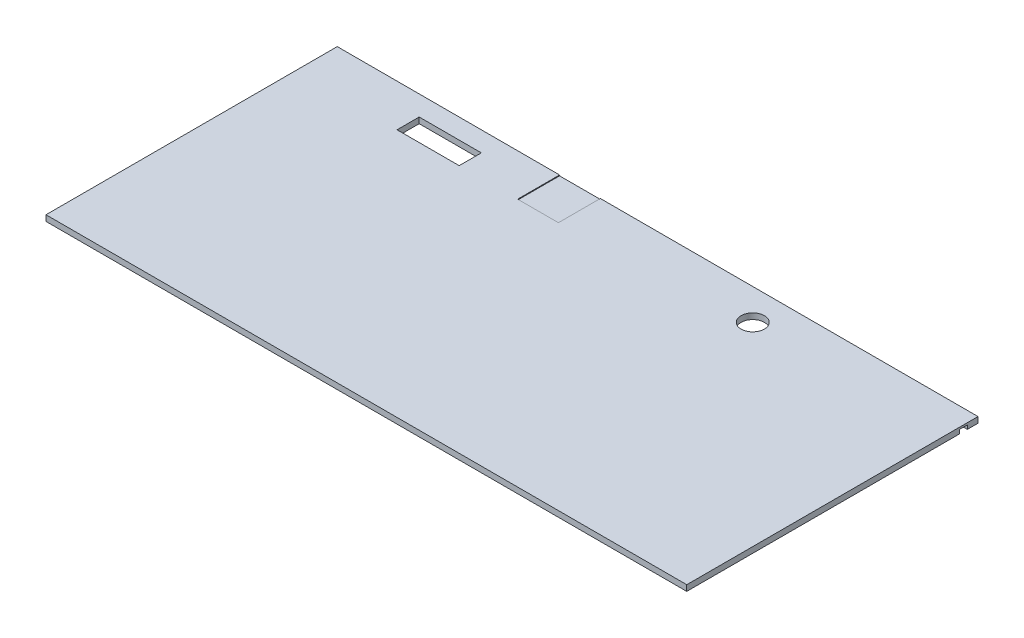
SolidWorks part; units mm, degrees
material "Oak"
ref_plane "Front Plane" through (0, 0, 0) normal (0, 0, 1) x (1, 0, 0)
ref_plane "Top Plane" through (0, 0, 0) normal (0, 1, 0) x (1, 0, 0)
ref_plane "Right Plane" through (0, 0, 0) normal (1, 0, 0) x (0, 0, -1)
sketch "Sketch1" plane through (0, 0, 0) normal (0, 1, 0) x (1, 0, 0)
  line L0 (425, 375) -> (425, -375) construction
  line L1 (-825, -375) -> (825, -375)
  line L2 (-825, -375) -> (-825, 375)
  line L3 (-825, 375) -> (825, 375)
  line L4 (825, -375) -> (825, 375)
  line L5 (-825, -375) -> (825, 375) construction
  line L6 (-825, 375) -> (825, -375) construction
  line L7 (425, 375) -> (-825, 375) construction
  line L8 (-200, 375) -> (-200, -375) construction
  line L9 (-252.5, 375) -> (-252.5, 267)
  line L10 (-252.5, 267) -> (-147.5, 267)
  line L11 (-147.5, 267) -> (-147.5, 375)
  line L12 (-482.5, 323.5) -> (-482.5, 266.5) construction
  line L13 (-562.5, 266.5) -> (-402.5, 266.5)
  line L14 (-562.5, 266.5) -> (-562.5, 323.5)
  line L15 (-562.5, 323.5) -> (-402.5, 323.5)
  line L16 (-402.5, 266.5) -> (-402.5, 323.5)
  circle A0 centre (325, 295) radius 30
  point P0 (0, 0)
  point P22 (-482.5, 295)
  dimension "D6" = 60
  dimension "D1" = 1650
  dimension "D2" = 750
  dimension "D3" = 400
  dimension "D4" = 105
  dimension "D5" = 108
  dimension "D7" = 80
  dimension "D8" = 100
  dimension "D9" = 160
  dimension "D10" = 57
  dimension "D11" = 80
  dimension "D12" = 150
extrude "Boss-Extrude1" add sketch "Sketch1" along normal blind 15 contours L11 L10 L9 L3 L2 L1 L4 A0 L16 L13 L14 L15 | L10 L11 L3 L9 region at (4.7352, 0, 5.9006) region at (-200, 0, -321)
sketch "Sketch3" plane through (0, 0, 0) normal (0, -1, 0) x (1, 0, 0)
  line L0 (-787.5, 300) -> (-787.5, -300) construction
  line L1 (-825, -375) -> (-750, -375) construction
  line L2 (-825, -375) -> (-825, -300) construction
  line L3 (-825, -300) -> (-750, -300) construction
  line L4 (-750, -375) -> (-750, -300) construction
  line L9 (7.7, 0) -> (-7.7, 0) construction
  line L10 (-825, 375) -> (-825, 300) construction
  line L11 (-825, 375) -> (-750, 375) construction
  line L12 (-750, 375) -> (-750, 300) construction
  line L13 (-825, 300) -> (-750, 300) construction
  line L14 (-777.5, 300) -> (-777.5, -300)
  line L15 (-797.5, -300) -> (-797.5, 300)
  line L16 (-797.5, 300) -> (-777.5, 300)
  line L17 (-777.5, -300) -> (-797.5, -300)
  dimension "D1" = 75
  dimension "D2" = 20
sketch "Sketch2" plane through (-825, 0, 0) normal (-1, 0, 0) x (0, 0, 1)
  line L0 (-300, 0) -> (-300, 15) construction
  line L1 (375, 0) -> (-375, 0) construction
  line L2 (375, 15) -> (-375, 15) construction
  line L3 (-375, 15) -> (-375, 0) construction
  line L4 (-300, 15) -> (-375, 15) construction
  line L5 (-337.5, 15) -> (-337.5, 0) construction
  line L6 (375, 0) -> (-375, 0) construction
  line L7 (-347.5, 0) -> (-347.5, 10)
  line L8 (-347.5, 10) -> (-327.5, 10)
  line L9 (-327.5, 10) -> (-327.5, 0)
  line L10 (-327.5, 0) -> (-347.5, 0)
  line L11 (0, -7.7) -> (0, 7.7) construction
  line L12 (347.5, 10) -> (327.5, 10)
  line L13 (347.5, 0) -> (347.5, 10)
  line L14 (327.5, 0) -> (347.5, 0)
  line L15 (327.5, 10) -> (327.5, 0)
  line M7 (-375, 0) -> (375, 0)
  dimension "D1" = 75
  dimension "D2" = 20
  dimension "D3" = 10
extrude "Cut-Extrude1" cut sketch "Sketch2" along normal up to vertex (-75 mm away) from vertex contours L9 L8 L7 M7 region at (-825, 5, -337.5) up to point (-750, 0, -300) starting at point (-252.5, 0, -375)
extrude "Cut-Extrude2" cut sketch "Sketch2<3>" against normal through all from vertex contours L9 L8 L7 M7 region at (-825, 5, -337.5) starting at point (-147.5, 0, -375)
sketch "Sketch2<3>" plane through (-825, 0, 0) normal (-1, 0, 0) x (0, 0, 1) same geometry as "Sketch2"
extrude "Cut-Extrude3" cut sketch "Sketch1<3>" along normal through all from offset 13 contours L10 L11 L3 L9 region at (-200, 0, -321)
sketch "Sketch1<3>" plane through (0, 0, 0) normal (0, 1, 0) x (1, 0, 0) same geometry as "Sketch1"
extrude "Cut-Extrude4" cut sketch "Sketch2<4>" against normal up to vertex (572.5 mm away) from vertex contours L12 L15 L13 M7 region at (-825, 5, 337.5) up to point (-252.5, 0, -267) starting at point (-750, 0, 375)
sketch "Sketch2<4>" plane through (-825, 0, 0) normal (-1, 0, 0) x (0, 0, 1) same geometry as "Sketch2"
extrude "Cut-Extrude5" cut sketch "Sketch2<5>" against normal up to vertex (1250 mm away) from vertex contours L12 L15 L13 M7 region at (-825, 5, 337.5) up to point (425, 0, 375) starting at point (-147.5, 0, -267)
sketch "Sketch2<5>" plane through (-825, 0, 0) normal (-1, 0, 0) x (0, 0, 1) same geometry as "Sketch2"
sketch "Sketch4" plane through (0, 0, 0) normal (0, -1, 0) x (1, 0, 0)
  line L0 (-252.5, -347.5) -> (-147.5, -347.5) construction
  line L1 (-200, -347.5) -> (-200, 347.5) construction
  line L2 (-252.5, 347.5) -> (-147.5, 347.5) construction
  line L3 (-252.5, -347.5) -> (-232.5, -347.5)
  line L4 (-232.5, -347.5) -> (-232.5, -327.5)
  line L5 (-232.5, -327.5) -> (-252.5, -327.5)
  line L6 (-252.5, -327.5) -> (-252.5, -347.5)
  line L7 (-167.5, -327.5) -> (-147.5, -327.5)
  line L8 (-167.5, -347.5) -> (-167.5, -327.5)
  line L9 (-147.5, -347.5) -> (-167.5, -347.5)
  line L10 (-147.5, -327.5) -> (-147.5, -347.5)
  line L11 (7.7, 0) -> (-7.7, 0) construction
  line L12 (-167.5, 347.5) -> (-167.5, 327.5)
  line L13 (-147.5, 347.5) -> (-167.5, 347.5)
  line L14 (-147.5, 327.5) -> (-147.5, 347.5)
  line L15 (-167.5, 327.5) -> (-147.5, 327.5)
  line L16 (-232.5, 327.5) -> (-252.5, 327.5)
  line L17 (-232.5, 347.5) -> (-232.5, 327.5)
  line L18 (-252.5, 347.5) -> (-232.5, 347.5)
  line L19 (-252.5, 327.5) -> (-252.5, 347.5)
  dimension "D1" = 20
  dimension "D2" = 20
extrude "Cut-Extrude6" cut sketch "Sketch4" against normal blind 5
extrude "Cut-Extrude7" cut sketch "Sketch3" against normal blind 10
equation "\"A\"= 125cm"
equation "\"B\"= 40cm"
equation "\"C\"= 75cm"
equation "\"D\"= 15mm"
equation "\"D1@Sketch1\"=\"A\"+\"B\""
equation "\"D2@Sketch1\"=\"C\""
equation "\"D3@Sketch1\"=\"B\""
equation "\"D1@Boss-Extrude1\"=\"D\""
equation "\"D19@Cut-Extrude3\"=\"D\"-2"
